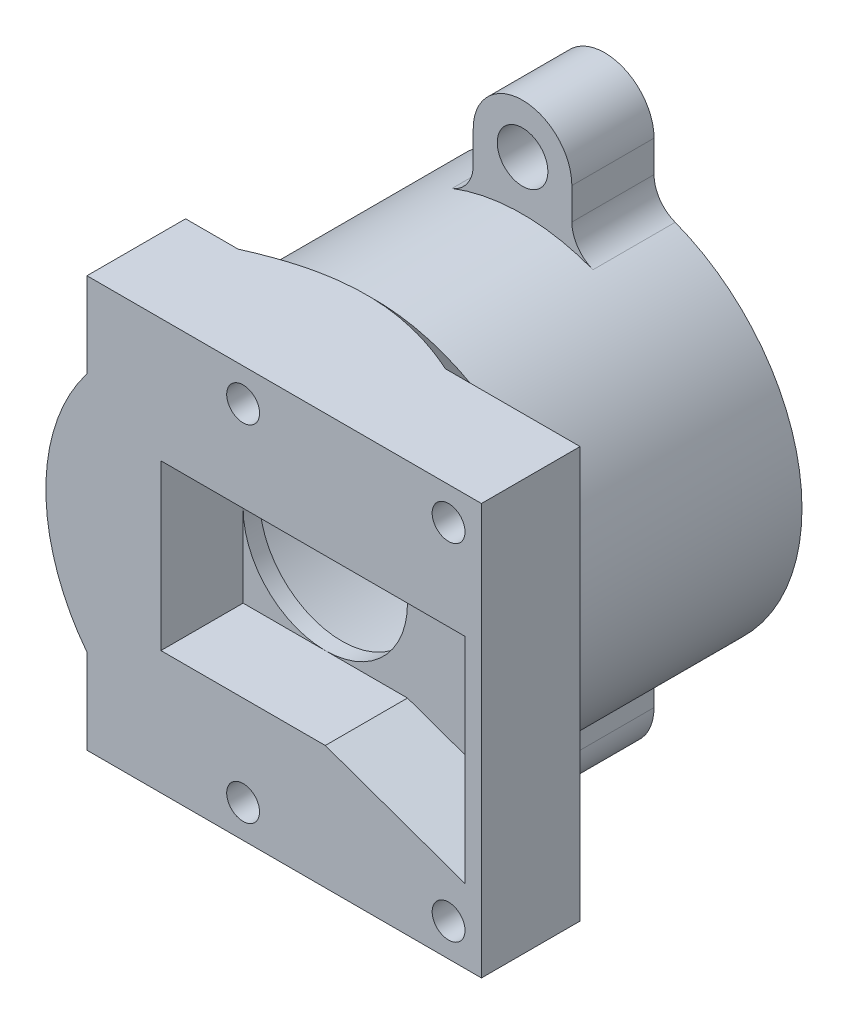
SolidWorks part; units mm, degrees
ref_plane "Front Plane" through (0, 0, 0) normal (1, 0, 0) x (0, 1, 0)
ref_plane "Top Plane" through (0, 0, 0) normal (0, 0, 1) x (0, 1, 0)
ref_plane "Right Plane" through (0, 0, 0) normal (0, 1, 0) x (-1, 0, 0)
sketch "Sketch1" plane through (0, 0, 0) normal (0, 0, 1) x (0, 1, 0)
  circle A0 centre (0, 0) radius 4.75
  circle A2 centre (0, 0) radius 12
extrude "Boss-Extrude1" add sketch "Sketch1" against normal blind 2 contours A2 | A2 A0 | A2 | A2 | A2 | A2 region at (0, -11.6606, 0)
sketch "Sketch2" plane through (0, 0, -2) normal (0, 0, -1) x (1, 0, 0)
  circle A0 centre (0, 0) radius 12
  circle A1 centre (0, 0) radius 10.8716
  point P4 (0, 0)
extrude "Boss-Extrude3" add sketch "Sketch2" along normal blind 20
sketch "Sketch3" plane through (0, 0, -22) normal (0, 0, -1) x (1, 0, 0)
  line L0 (0, 0) -> (0, 15)
  line L1 (-3, 15) -> (-3, 11.619)
  line L2 (3, 15) -> (3, 11.619)
  line L3 (0, 0) -> (3, 0)
  line L4 (-3, -15) -> (-3, -11.619)
  line L5 (3, -15) -> (3, -11.619)
  circle A0 centre (0, 0) radius 12
  circle A1 centre (0, 15) radius 3
  circle A2 centre (0, 15) radius 1.5391
  circle A3 centre (0, -15) radius 3
  circle A4 centre (0, -15) radius 1.5391
  circle M7 centre (0, 0) radius 12
extrude "Boss-Extrude4" add sketch "Sketch3" against normal blind 5 contours A1 L1 M7 | A1 L2 M7 | A2 A1 | L4 A3 M7 | A0 A3 L5 | A3 A4 region at (2.3172, -12.5416, -22) region at (-2.3172, -12.5416, -22) region at (-2.0613, -12.9387, -22) region at (-2.3172, 12.5416, -22) region at (2.3172, 12.5416, -22) region at (-2.0613, 12.9387, -22)
sketch "Sketch5" plane through (0, 0, 0) normal (0, 0, 1) x (1, 0, 0)
  line L0 (0, 0) -> (14.5, 0)
  line L1 (0, 0) -> (0, 10.5)
  line L2 (14.5, 0) -> (-9.5, 0)
  line L3 (14.5, -12.5) -> (14.5, 12.5)
  line L4 (14.5, 12.5) -> (-9.5, 12.5)
  line L5 (-9.5, -12.5) -> (-9.5, 12.5)
  line L6 (0, 10.5) -> (12.5, 10.5)
  line L7 (14.5, -12.5) -> (-9.5, -12.5)
  line L8 (13.5, -5) -> (13.5, -8.0225)
  line L9 (-5, -5) -> (5, -5)
  line L10 (-5, -5) -> (-5, 5)
  line L11 (-5, 5) -> (5, 5)
  line L12 (5, -5) -> (5, 5)
  line L13 (-5, -5) -> (5, 5) construction
  line L14 (-5, 5) -> (5, -5) construction
  line L15 (5, 5) -> (13.5, 5)
  line L16 (5, 5) -> (5, -5)
  line L17 (5, -5) -> (13.5, -5)
  line L18 (13.5, 5) -> (13.5, -5)
  line L19 (13.5, -8.0225) -> (5, -5)
  circle A0 centre (0, 10.5) radius 1
  circle A1 centre (12.5, 10.5) radius 1
  circle A2 centre (0, -10.5) radius 1
  circle A3 centre (12.5, -10.5) radius 1
  circle A4 centre (0, 0) radius 12
  circle M12 centre (0, 0) radius 4.75
  circle M13 centre (0, 0) radius 12
  dimension "D4" = 10
  dimension "D1" = 14.5
  dimension "D2" = 24
  dimension "D3" = 12.5
  dimension "D5" = 10
  dimension "D6" = 8.5
extrude "Boss-Extrude5" add sketch "Sketch5" against normal blind 5 contours A0 L1 L11 L15 L6 M13 | A1 L15 L18 L2 L3 L4 L5 M13 | A0 L6 L5 L2 L10 L11 L1 M13 | L19 L9 L10 L2 L5 A2 M13 | L8 L19 L5 L7 L3 L2 L18 A3 M13 | L5 M13 region at (-4.6617, 6.5575, 0) region at (4.6373, 7.4557, 0) region at (-1.5594, -6.9537, 0) region at (-10.5095, 0, 0) region at (13.7706, 2.5, 0) region at (14, -0.2706, 0)
extrude "Cut-Extrude4" cut sketch "Sketch5<4>" against normal blind 5 contours L11 L10 L2 L1 M12 | L0 L12 L11 L1 M12 | L9 L12 L0 L2 L10 M12 | L6 A0 L1 | L1 A0 L6 | A2 | L12 L17 L2 M13 | L15 L12 L2 M13 | L19 L17 M13 region at (3.6783, 3.6783, 0) region at (4.875, -0.1118, 0) region at (-3.6783, 3.6783, 0) region at (8.3294, 2.4322, 0) region at (8.3294, -2.4322, 0) region at (8.6297, -5.5866, 0) region at (-0.1415, 10.6415, 0) region at (0.4244, 10.0756, 0) region at (0, -10.5, 0)
sketch "Sketch5<4>" plane through (0, 0, 0) normal (0, 0, 1) x (1, 0, 0) same geometry as "Sketch5"
sketch "Sketch6" plane through (0, 0, -5) normal (0, 0, -1) x (1, 0, 0)
  line L0 (14.5, 12.5) -> (14.5, -12.5) construction
  line L1 (-9.5, 12.5) -> (14.5, 12.5)
  line L2 (-9.5, 12.5) -> (-9.5, -12.5)
  line L3 (-9.5, -12.5) -> (14.5, -12.5)
  line L4 (14.5, 12.5) -> (14.5, -12.5)
  circle A0 centre (0, 0) radius 12
  circle M1 centre (12.5, 10.5) radius 1
  circle M2 centre (12.5, -10.5) radius 1
  arc M3 (-9.5, 7.3314) -> (9.9215, 6.75) centre (0, 0) cw
  line M4 (9.9215, 6.75) -> (13.5, 8.0225)
  line M5 (13.5, 8.0225) -> (13.5, -5)
  line M6 (13.5, -5) -> (10.9087, -5)
  arc M7 (10.9087, -5) -> (-9.5, -7.3314) centre (0, 0) cw
  line M8 (-9.5, -7.3314) -> (-9.5, -12.5)
  line M9 (-9.5, -12.5) -> (14.5, -12.5)
  line M10 (14.5, -12.5) -> (14.5, 12.5)
  line M11 (14.5, 12.5) -> (-9.5, 12.5)
  line M12 (-9.5, 12.5) -> (-9.5, 7.3314)
extrude "Boss-Extrude11" add sketch "Sketch6" along normal blind 1 contours M12 M3 M4 M5 M6 M7 M8 M9 M10 M11 M2 M1 | A0 M6 M5 M4 | M1 | M2 region at (2.5, -12.1534, -5) region at (12.404, -1.8318, -5) region at (12.5, -10.5, -5) region at (12.5, 10.5, -5)
chamfer "Chamfer1" distance 2 angle 45 1 edges at (12, 0, -6)
combine bodies "Combine1" operation type add bodies to combine 105 108 111
fillet "Fillet2" radius 2 4 edges at (3, 11.619, -19.5) (3, -11.619, -19.5) (-3, 11.619, -19.5) (-3, -11.619, -19.5)
sketch "Sketch7" plane through (0, 0, -5) normal (0, 0, -1) x (1, 0, 0)
  circle A0 centre (0, 0) radius 5
  circle A1 centre (0, 0) radius 12
  arc M1 (0.9438, -10.8306) -> (9.6536, -5) centre (0, 0) ccw
  line M2 (9.6536, -5) -> (-5, -5)
  line M3 (-5, -5) -> (-5, 5)
  line M4 (-5, 5) -> (5, 5)
  line M5 (5, 5) -> (8.8187, 6.3579)
  arc M6 (8.8187, 6.3579) -> (0.9438, 10.8306) centre (0, 0) ccw
  arc M7 (0.9438, 10.8306) -> (-0.9438, 10.8306) centre (0, 10.5) cw
  arc M8 (-0.9438, 10.8306) -> (-0.9438, -10.8306) centre (0, 0) ccw
  arc M9 (-0.9438, -10.8306) -> (0.9438, -10.8306) centre (0, -10.5) cw
extrude "Boss-Extrude13" add sketch "Sketch7" along normal blind 1 contours M9 M1 M2 M3 M4 M5 M6 M7 M8 | A1 A0 M2 M1 M9 M8 M7 M6 M5 M4 | A0 M4 M3 | A0 M3 M2 region at (-3.8832, -3.8832, -5) region at (-2.5, -5.2984, -5) region at (-3.8832, 3.8832, -5) region at (-11.6606, 0, -5)
